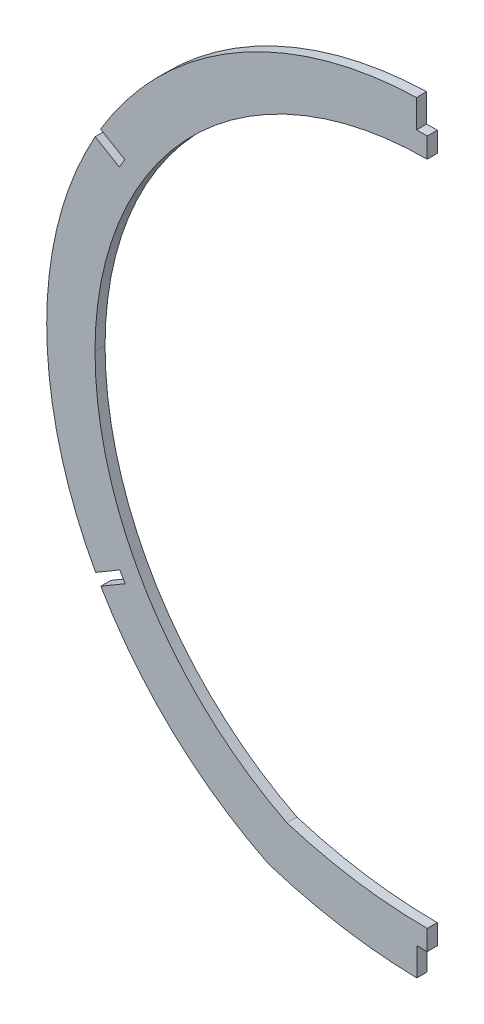
SolidWorks part; units mm, degrees
material "Balsa"
ref_plane "Front Plane" through (0, 0, 0) normal (0, 0, 1) x (1, 0, 0)
ref_plane "Top Plane" through (0, 0, 0) normal (0, 1, 0) x (1, 0, 0)
ref_plane "Right Plane" through (0, 0, 0) normal (1, 0, 0) x (0, 0, -1)
sketch "Sketch2" plane through (0, 0, 0) normal (0, 0, 1) x (1, 0, 0)
  line L0 (0, 0) -> (0.688, 245.4392) construction
  line L1 (-0.1309, -46.7153) -> (-0.2841, -101.3462) construction
  line L2 (0.0534, 19.05) -> (-169.3081, 19.05) construction
  line L3 (-72.7218, -93.726) -> (74.7111, -93.726) construction
  arc A1 (-120.0989, 19.05) -> (120.2036, 18.3433) centre (0.0534, 19.05) cw
  arc A2 (-120.0989, 19.05) -> (-50.0584, -93.726) centre (5.7147, 19.05) ccw
  arc A3 (-50.0584, -93.726) -> (50.1388, -93.726) centre (0.0402, 63.5) ccw
  arc A4 (120.2036, 18.3433) -> (50.1388, -93.726) centre (-5.6406, 19.0835) cw
  arc A5 (-104.8589, 19.05) -> (104.9639, 18.4329) centre (0.0534, 19.05) cw
  arc A6 (104.9639, 18.4329) -> (44.4049, -79.5534) centre (-5.6406, 19.0835) cw
  arc A7 (-44.324, -79.5535) -> (44.4049, -79.5534) centre (0.0402, 63.5) ccw
  arc A8 (-104.8589, 19.05) -> (-44.324, -79.5535) centre (5.7147, 19.05) ccw
  spline S0 degree 3 poles (-5521.0274, 5583.2546) (-1226.7801, 553.2855) (-196.9505, -260.8007) (69.4764, -82.4823) (75.8596, -77.7331) (81.7614, -72.3621) (85.2966, -68.8071) (85.996, -68.0862) (87.3792, -66.6243) (88.0639, -65.8824) (90.0847, -63.6371) (91.3894, -62.1126) (95.1787, -57.4581) (97.5389, -54.2471) (101.9343, -47.6137) (103.9694, -44.1914) (106.7765, -38.8981) (107.6712, -37.107) (109.3772, -33.4707) (110.1904, -31.6207) (112.481, -26.0415) (113.8153, -22.2742) (116.1105, -14.6467) (117.0712, -10.7866) (118.62, -2.9737) (119.208, 0.9791) (119.8028, 6.9796) (119.953, 8.9949) (120.1541, 13.0067) (120.2055, 15.0081) (120.2151, 20.9991) (119.8425, 28.9519) (118.7088, 36.835) (117.5685, 42.7208) (117.1399, 44.6783) (116.1841, 48.5842) (115.6559, 50.5346) (113.94, 56.3082) (112.6165, 60.0751) (109.6192, 67.4485) (107.9453, 71.055) (104.2453, 78.1066) (102.2192, 81.5518) (99.4588, 85.754) (98.8945, 86.5903) (97.7468, 88.2466) (97.1639, 89.0659) (95.3883, 91.4977) (94.1686, 93.0841) (90.4034, 97.7402) (87.752, 100.7072) (82.1689, 106.369) (79.2371, 109.0639) (74.6247, 112.8977) (73.0514, 114.1408) (70.6363, 115.9521) (69.821, 116.5478) (68.1799, 117.7153) (67.3537, 118.2875) (63.1947, 121.0918) (59.7778, 123.1535) (52.769, 126.9212) (49.1769, 128.6272) (41.816, 131.6806) (38.0473, 133.028) (33.2217, 134.4796) (32.2518, 134.758) (30.3116, 135.2882) (29.34, 135.5404) (26.4206, 136.2591) (24.4685, 136.6873) (18.5945, 137.8219) (14.6552, 138.3782) (6.7301, 139.0933) (2.7444, 139.252) (-2.2675, 139.1959) (-3.2714, 139.172) (-5.2821, 139.0983) (-6.2905, 139.0484) (-9.3072, 138.8606) (-11.3068, 138.6846) (-17.272, 138.0072) (-25.1357, 136.7069) (-32.823, 134.6274) (-38.5216, 132.7724) (-40.41, 132.1048) (-44.1641, 130.6694) (-46.0326, 129.9002) (-465.435, -55.3606) (264.7727, -2591.6725) (2155.1784, -7505.3224) knots -2.450405 -2.450405 -2.450405 -2.450405 0.03125 0.03125 0.0625 0.09375 0.09375 0.101563 0.101563 0.109375 0.109375 0.125 0.125 0.15625 0.15625 0.1875 0.1875 0.203125 0.203125 0.21875 0.21875 0.25 0.25 0.28125 0.28125 0.3125 0.3125 0.328125 0.328125 0.34375 0.34375 0.375 0.40625 0.40625 0.421875 0.421875 0.4375 0.4375 0.46875 0.46875 0.5 0.5 0.53125 0.53125 0.539063 0.539063 0.546875 0.546875 0.5625 0.5625 0.59375 0.59375 0.625 0.625 0.640625 0.640625 0.648438 0.648438 0.65625 0.65625 0.6875 0.6875 0.71875 0.71875 0.75 0.75 0.757813 0.757813 0.765625 0.765625 0.78125 0.78125 0.8125 0.8125 0.84375 0.84375 0.851563 0.851563 0.859375 0.859375 0.875 0.875 0.90625 0.9375 0.9375 0.953125 0.953125 0.96875 0.96875 4.508313 4.508313 4.508313 4.508313 only from (55.8537, -90.8749) to (-58.6671, 123.6507)
  spline S1 degree 3 poles (55.8537, -90.8749) (59.4151, -88.9779) (62.8499, -86.9173) (69.4764, -82.4823) (75.8596, -77.7331) (81.7614, -72.3621) (85.2966, -68.8071) (85.996, -68.0862) (87.3792, -66.6243) (88.0639, -65.8824) (90.0847, -63.6371) (91.3894, -62.1126) (95.1787, -57.4581) (97.5389, -54.2471) (101.9343, -47.6137) (103.9694, -44.1914) (106.7765, -38.8981) (107.6712, -37.107) (109.3772, -33.4707) (110.1904, -31.6207) (112.481, -26.0415) (113.8153, -22.2742) (116.1105, -14.6467) (117.0712, -10.7866) (118.62, -2.9737) (119.208, 0.9791) (119.8028, 6.9796) (119.953, 8.9949) (120.1541, 13.0067) (120.2055, 15.0081) (120.2151, 20.9991) (119.8425, 28.9519) (118.7088, 36.835) (117.5685, 42.7208) (117.1399, 44.6783) (116.1841, 48.5842) (115.6559, 50.5346) (113.94, 56.3082) (112.6165, 60.0751) (109.6192, 67.4485) (107.9453, 71.055) (104.2453, 78.1066) (102.2192, 81.5518) (99.4588, 85.754) (98.8945, 86.5903) (97.7468, 88.2466) (97.1639, 89.0659) (95.3883, 91.4977) (94.1686, 93.0841) (90.4034, 97.7402) (87.752, 100.7072) (82.1689, 106.369) (79.2371, 109.0639) (74.6247, 112.8977) (73.0514, 114.1408) (70.6363, 115.9521) (69.821, 116.5478) (68.1799, 117.7153) (67.3537, 118.2875) (63.1947, 121.0918) (59.7778, 123.1535) (52.769, 126.9212) (49.1769, 128.6272) (41.816, 131.6806) (38.0473, 133.028) (33.2217, 134.4796) (32.2518, 134.758) (30.3116, 135.2882) (29.34, 135.5404) (26.4206, 136.2591) (24.4685, 136.6873) (18.5945, 137.8219) (14.6552, 138.3782) (6.7301, 139.0933) (2.7444, 139.252) (-2.2675, 139.1959) (-3.2714, 139.172) (-5.2821, 139.0983) (-6.2905, 139.0484) (-9.3072, 138.8606) (-11.3068, 138.6846) (-17.272, 138.0072) (-25.1357, 136.7069) (-32.823, 134.6274) (-38.5216, 132.7724) (-40.41, 132.1048) (-44.1641, 130.6694) (-46.0326, 129.9002) (-51.5624, 127.4576) (-55.1595, 125.6458) (-58.6671, 123.6507) knots 0 0 0 0 0.03125 0.03125 0.0625 0.09375 0.09375 0.101563 0.101563 0.109375 0.109375 0.125 0.125 0.15625 0.15625 0.1875 0.1875 0.203125 0.203125 0.21875 0.21875 0.25 0.25 0.28125 0.28125 0.3125 0.3125 0.328125 0.328125 0.34375 0.34375 0.375 0.40625 0.40625 0.421875 0.421875 0.4375 0.4375 0.46875 0.46875 0.5 0.5 0.53125 0.53125 0.539063 0.539063 0.546875 0.546875 0.5625 0.5625 0.59375 0.59375 0.625 0.625 0.640625 0.640625 0.648438 0.648438 0.65625 0.65625 0.6875 0.6875 0.71875 0.71875 0.75 0.75 0.757813 0.757813 0.765625 0.765625 0.78125 0.78125 0.8125 0.8125 0.84375 0.84375 0.851563 0.851563 0.859375 0.859375 0.875 0.875 0.90625 0.9375 0.9375 0.953125 0.953125 0.96875 0.96875 1 1 1 1 construction
  spline S2 degree 3 poles (5694.5744, -5369.3669) (1292.3799, -516.6509) (187.1926, 314.492) (-76.9523, 111.0297) (-81.0984, 107.3558) (-85.9766, 102.3921) (-86.9369, 101.3807) (-88.8267, 99.3202) (-89.7577, 98.2691) (-92.4915, 95.0728) (-94.2304, 92.8907) (-99.2026, 86.1952) (-102.1931, 81.5333) (-106.1993, 74.2476) (-107.4545, 71.77) (-109.2154, 67.9791) (-109.782, 66.7031) (-110.874, 64.1258) (-111.4002, 62.8224) (-113.9097, 56.2871) (-115.5417, 50.9767) (-118.0823, 40.1978) (-118.9908, 34.7292) (-119.6657, 27.7928) (-119.7775, 26.4005) (-119.9543, 23.6055) (-120.0192, 22.2016) (-120.1418, 18.0057) (-120.1286, 15.2199) (-119.8102, 6.8959) (-119.2278, 1.3912) (-117.8014, -6.7994) (-117.2335, -9.5184) (-116.2404, -13.58) (-115.8858, -14.9311) (-115.1288, -17.6274) (-114.7258, -18.9739) (-112.6063, -25.6411) (-108.5276, -35.9696) (-103.1136, -45.6397) (-99.3011, -51.4722) (-98.5171, -52.628) (-96.9053, -54.9182) (-96.0765, -56.0537) (-93.5433, -59.4015) (-91.7865, -61.5635) (-86.3167, -67.8444) (-82.4051, -71.759) (-76.1398, -77.2217) (-73.9848, -78.9742) (-70.6503, -81.498) (-69.5218, -82.3217) (-67.2303, -83.9337) (-66.0665, -84.7222) (540.7318, -480.5341) (3882.3497, 5108.7967) (222.2795, -4616.5222) knots -3.63779 -3.63779 -3.63779 -3.63779 0.0625 0.0625 0.125 0.125 0.140625 0.140625 0.15625 0.15625 0.1875 0.1875 0.25 0.25 0.28125 0.28125 0.296875 0.296875 0.3125 0.3125 0.375 0.375 0.4375 0.4375 0.453125 0.453125 0.46875 0.46875 0.5 0.5 0.5625 0.5625 0.59375 0.59375 0.609375 0.609375 0.625 0.625 0.6875 0.75 0.75 0.765625 0.765625 0.78125 0.78125 0.8125 0.8125 0.875 0.875 0.90625 0.90625 0.921875 0.921875 0.9375 0.9375 9.012836 9.012836 9.012836 9.012836 only from (-58.6671, 123.6507) to (-50.3455, -93.5936)
  spline S3 degree 3 poles (-4578.1193, 6360.5009) (1102.8247, -3189.0685) (1357.3206, -1629.0846) (-2110.3169, 7551.2134) knots -196.711406 -196.711406 -196.711406 -196.711406 209.883914 209.883914 209.883914 209.883914 only from (49.819, -93.8744) to (55.8537, -90.8749)
  spline S4 degree 3 poles (49.819, -93.8744) (51.8584, -92.9316) (53.87, -91.9317) (55.8537, -90.8749) knots 0 0 0 0 1 1 1 1 construction
  spline S5 degree 3 poles (-58.6671, 123.6507) (-63.5487, 120.874) (-68.1774, 117.7887) (-76.9523, 111.0297) (-81.0984, 107.3558) (-85.9766, 102.3921) (-86.9369, 101.3807) (-88.8267, 99.3202) (-89.7577, 98.2691) (-92.4915, 95.0728) (-94.2304, 92.8907) (-99.2026, 86.1952) (-102.1931, 81.5333) (-106.1993, 74.2476) (-107.4545, 71.77) (-109.2154, 67.9791) (-109.782, 66.7031) (-110.874, 64.1258) (-111.4002, 62.8224) (-113.9097, 56.2871) (-115.5417, 50.9767) (-118.0823, 40.1978) (-118.9908, 34.7292) (-119.6657, 27.7928) (-119.7775, 26.4005) (-119.9543, 23.6055) (-120.0192, 22.2016) (-120.1418, 18.0057) (-120.1286, 15.2199) (-119.8102, 6.8959) (-119.2278, 1.3912) (-117.8014, -6.7994) (-117.2335, -9.5184) (-116.2404, -13.58) (-115.8858, -14.9311) (-115.1288, -17.6274) (-114.7258, -18.9739) (-112.6063, -25.6411) (-108.5276, -35.9696) (-103.1136, -45.6397) (-99.3011, -51.4722) (-98.5171, -52.628) (-96.9053, -54.9182) (-96.0765, -56.0537) (-93.5433, -59.4015) (-91.7865, -61.5635) (-86.3167, -67.8444) (-82.4051, -71.759) (-76.1398, -77.2217) (-73.9848, -78.9742) (-70.6503, -81.498) (-69.5218, -82.3217) (-67.2303, -83.9337) (-66.0665, -84.7222) (-60.2073, -88.5441) (-55.3561, -91.2432) (-50.3455, -93.5936) knots 0 0 0 0 0.0625 0.0625 0.125 0.125 0.140625 0.140625 0.15625 0.15625 0.1875 0.1875 0.25 0.25 0.28125 0.28125 0.296875 0.296875 0.3125 0.3125 0.375 0.375 0.4375 0.4375 0.453125 0.453125 0.46875 0.46875 0.5 0.5 0.5625 0.5625 0.59375 0.59375 0.609375 0.609375 0.625 0.625 0.6875 0.75 0.75 0.765625 0.765625 0.78125 0.78125 0.8125 0.8125 0.875 0.875 0.90625 0.90625 0.921875 0.921875 0.9375 0.9375 1 1 1 1 construction
  spline S6 degree 3 poles (-1759.0643, 7695.5768) (129.301, 75.0658) (104.9025, -75.6984) (45.8458, -95.3665) (44.8322, -95.6594) (41.7708, -96.4587) (39.7032, -96.8873) (35.5384, -97.6293) (33.4392, -97.9405) (29.2422, -98.4783) (27.1412, -98.7049) (20.8322, -99.2882) (16.6185, -99.55) (8.1799, -99.8877) (3.9548, -99.9623) (-4.5058, -99.9387) (-8.734, -99.8405) (-17.1695, -99.4557) (-21.3793, -99.1705) (-27.6778, -98.553) (-29.7745, -98.3152) (-33.9608, -97.7556) (-36.0504, -97.4344) (-39.177, -96.8603) (-40.2191, -96.653) (-42.292, -96.1992) (-43.3225, -95.953) (-45.3676, -95.407) (-46.3821, -95.1076) (-105.8729, -74.9194) (-124.4058, 77.5041) (2082.3243, 7613.4914) knots -1.777254 -1.777254 -1.777254 -1.777254 0.03125 0.03125 0.0625 0.0625 0.125 0.125 0.1875 0.1875 0.25 0.25 0.375 0.375 0.5 0.5 0.625 0.625 0.75 0.75 0.8125 0.8125 0.875 0.875 0.90625 0.90625 0.9375 0.9375 0.96875 0.96875 2.792352 2.792352 2.792352 2.792352 only from (49.8185, -93.8746) to (-50.3451, -93.5938)
  spline S7 degree 3 poles (49.8185, -93.8746) (48.8452, -94.325) (47.8521, -94.6984) (45.8458, -95.3665) (44.8322, -95.6594) (41.7708, -96.4587) (39.7032, -96.8873) (35.5384, -97.6293) (33.4392, -97.9405) (29.2422, -98.4783) (27.1412, -98.7049) (20.8322, -99.2882) (16.6185, -99.55) (8.1799, -99.8877) (3.9548, -99.9623) (-4.5058, -99.9387) (-8.734, -99.8405) (-17.1695, -99.4557) (-21.3793, -99.1705) (-27.6778, -98.553) (-29.7745, -98.3152) (-33.9608, -97.7556) (-36.0504, -97.4344) (-39.177, -96.8603) (-40.2191, -96.653) (-42.292, -96.1992) (-43.3225, -95.953) (-45.3676, -95.407) (-46.3821, -95.1076) (-48.3867, -94.4274) (-49.3773, -94.0483) (-50.3451, -93.5938) knots 0 0 0 0 0.03125 0.03125 0.0625 0.0625 0.125 0.125 0.1875 0.1875 0.25 0.25 0.375 0.375 0.5 0.5 0.625 0.625 0.75 0.75 0.8125 0.8125 0.875 0.875 0.90625 0.90625 0.9375 0.9375 0.96875 0.96875 1 1 1 1 construction
  spline S8 degree 1 poles (44.4895, -82.3468) (49.8828, -79.6661) knots 0 0 1 1 construction
  spline S9 degree 1 poles (49.8828, -79.6661) (-52.388, 112.6115) knots 0 0 1 1 construction
  spline S10 degree 1 poles (-52.388, 112.6115) (-44.952, -82.0958) knots 0 0 1 1 construction
  spline S11 degree 3 poles (44.4895, -82.3468) (44.9451, -82.1361) (45.8533, -81.7084) (47.2062, -81.0479) (48.5497, -80.3682) (49.4396, -79.9022) (49.8828, -79.6661) knots 0 0 0 0 0.250007 0.500014 0.750021 1.000028 1.000028 1.000028 1.000028 construction
  spline S12 degree 3 poles (49.8828, -79.6661) (51.4682, -78.8216) (54.6039, -77.0481) (60.6329, -73.2256) (67.7713, -67.9145) (75.6946, -60.7068) (85.376, -49.946) (92.2499, -39.5527) (97.0635, -29.9209) (99.9774, -23.2906) (102.9687, -14.8438) (105.5551, -4.452) (106.8747, 4.4138) (107.4138, 11.642) (107.598, 18.8242) (107.1791, 27.7507) (105.6575, 38.3493) (103.0737, 48.9109) (99.5091, 59.0529) (95.0071, 68.7524) (90.4672, 76.4728) (86.3465, 82.4205) (79.7918, 90.9419) (71.0678, 99.805) (59.5047, 108.4813) (50.3361, 114.0108) (40.7123, 118.5824) (32.2831, 121.5955) (25.3334, 123.4944) (18.366, 125.0225) (9.571, 126.2643) (-1.0997, 126.6912) (-11.9104, 126.0185) (-22.4327, 124.2743) (-36.1547, 120.5693) (-46.1487, 116.1604) (-52.388, 112.6115) knots 0 0 0 0 0.015625 0.03125 0.0625 0.09375 0.125 0.1875 0.203125 0.21875 0.25 0.28125 0.3125 0.328125 0.34375 0.375 0.40625 0.4375 0.46875 0.5 0.53125 0.546875 0.5625 0.625 0.65625 0.6875 0.71875 0.75 0.765625 0.78125 0.8125 0.84375 0.875 0.90625 0.9375 1 1 1 1 construction
  spline S13 degree 3 poles (-52.388, 112.6115) (-54.5585, 111.3769) (-58.8261, 108.7475) (-66.8816, 102.9693) (-76.1597, 94.757) (-85.9932, 83.258) (-92.681, 72.8203) (-97.1816, 63.9424) (-101.112, 54.6656) (-104.776, 42.7383) (-106.8137, 30.488) (-107.4512, 20.4245) (-107.4028, 10.4189) (-106.3564, 0.5368) (-104.3212, -9.2152) (-101.5955, -18.9231) (-97.0158, -30.5128) (-90.9605, -41.334) (-85.1677, -49.567) (-78.8706, -57.3154) (-71.8665, -64.3232) (-64.1621, -70.5906) (-57.9948, -74.9291) (-51.5954, -78.7902) (-47.193, -81.0446) (-44.952, -82.0958) knots 0 0 0 0 0.03125 0.0625 0.125 0.1875 0.25 0.28125 0.3125 0.375 0.4375 0.46875 0.5 0.5625 0.59375 0.625 0.6875 0.75 0.78125 0.8125 0.875 0.90625 0.9375 0.96875 1 1 1 1 construction
  spline S14 degree 1 poles (44.4849, -82.3489) (-44.9469, -82.0982) knots 0 0 1 1 construction
  spline S15 degree 3 poles (44.4849, -82.3489) (44.3746, -82.3999) (44.1627, -82.4934) (43.6492, -82.7012) (42.8561, -82.9839) (41.7841, -83.3184) (40.2245, -83.7477) (38.1103, -84.2445) (35.4106, -84.7656) (32.6063, -85.224) (28.7759, -85.7537) (23.885, -86.2821) (17.9201, -86.7432) (11.8971, -87.0512) (5.8396, -87.2261) (-2.2666, -87.2864) (-10.3738, -87.0974) (-18.3985, -86.6419) (-24.3556, -86.1481) (-29.2377, -85.5934) (-33.056, -85.0443) (-35.8555, -84.5718) (-38.5671, -84.0318) (-40.6899, -83.5223) (-42.2517, -83.0828) (-43.3238, -82.7417) (-44.1147, -82.4546) (-44.6269, -82.2439) (-44.8373, -82.1497) (-44.9469, -82.0982) knots 0 0 0 0 0.007812 0.015625 0.03125 0.046875 0.0625 0.09375 0.125 0.15625 0.1875 0.25 0.3125 0.375 0.4375 0.5 0.625 0.6875 0.75 0.8125 0.84375 0.875 0.90625 0.9375 0.953125 0.96875 0.984375 0.992188 1 1 1 1 construction
  point P12 (-0.2802, -99.9505)
  dimension "D3" = 19.05
  dimension "D4" = 93.726
  dimension "D5" = 63.5
  dimension "D6" = 15.24
  dimension "D1" = 12.7
  dimension "D2" = 12.7
extrude "Boss-Extrude1" add sketch "Sketch2" along normal mid plane 3.175
sketch "Sketch3" plane through (0, 0, 0) normal (1, 0, 0) x (0, 0, -1)
  line L1 (-100.0568, 212.3798) -> (108.5889, 212.3798)
  line L2 (-100.0568, 212.3798) -> (-100.0568, -170.6472)
  line L3 (-100.0568, -170.6472) -> (108.5889, -170.6472)
  line L4 (108.5889, 212.3798) -> (108.5889, -170.6472)
extrude "Cut-Extrude1" cut sketch "Sketch3" along normal through all
sketch "Sketch4" plane through (0, 0, 1.5875) normal (0, 0, 1) x (1, 0, 0)
  line L0 (0, 0) -> (0, 123.9623) construction
  line L1 (0, 123.9623) -> (0, 130.3123) construction
  line L2 (-3.3782, 130.3123) -> (3.3782, 130.3123)
  line L3 (0, 130.3123) -> (0, 143.0123)
  line L4 (3.3782, 130.3123) -> (3.3782, 143.0123)
  line L5 (-3.3782, 143.0123) -> (3.3782, 143.0123)
  line L6 (90.8212, 71.4752) -> (96.2977, 74.6892) construction
  line L7 (95.4428, 76.146) -> (97.1526, 73.2325)
  line L8 (90.8212, 71.4752) -> (0, 18.1749) construction
  line L9 (95.4428, 76.146) -> (106.3959, 82.5741)
  line L10 (97.1526, 73.2325) -> (108.1057, 79.6605)
  line L11 (106.3959, 82.5741) -> (108.1057, 79.6605)
  line L12 (90.7135, -35.0622) -> (96.19, -38.2762) construction
  line L13 (90.7135, -35.0622) -> (0, 18.1749) construction
  line L14 (95.3351, -39.733) -> (97.045, -36.8194)
  line L15 (95.3351, -39.733) -> (106.2882, -46.161)
  line L16 (97.045, -36.8194) -> (107.998, -43.2475)
  line L17 (106.2882, -46.161) -> (107.998, -43.2475)
  line L18 (0, 0) -> (0, -86.2748) construction
  line L19 (0, -86.2748) -> (0, -92.6248) construction
  line L20 (-3.302, -92.6248) -> (3.302, -92.6248)
  line L21 (0, -92.6248) -> (0, -105.3248)
  line L22 (3.302, -92.6248) -> (3.302, -105.3248)
  line L23 (-3.302, -105.3248) -> (3.302, -105.3248)
  line L24 (-90.7135, -35.0622) -> (0, 18.1749) construction
  line L25 (-90.7135, -35.0622) -> (-96.19, -38.2762) construction
  line L26 (-90.8212, 71.4752) -> (0, 18.1749) construction
  line L27 (-90.8212, 71.4752) -> (-96.2977, 74.6892) construction
  line L28 (-3.302, -92.6248) -> (-3.302, -105.3248)
  line L29 (-106.2882, -46.161) -> (-107.998, -43.2475)
  line L30 (-97.045, -36.8194) -> (-107.998, -43.2475)
  line L31 (-95.3351, -39.733) -> (-106.2882, -46.161)
  line L32 (-95.3351, -39.733) -> (-97.045, -36.8194)
  line L33 (-106.3959, 82.5741) -> (-108.1057, 79.6605)
  line L34 (-97.1526, 73.2325) -> (-108.1057, 79.6605)
  line L35 (-95.4428, 76.146) -> (-106.3959, 82.5741)
  line L36 (-95.4428, 76.146) -> (-97.1526, 73.2325)
  line L37 (-3.3782, 130.3123) -> (-3.3782, 143.0123)
  point P2 (96.2977, 74.6892)
  point P10 (96.19, -38.2762)
  point P26 (0, 0)
  point P44 (0, 0)
  point P45 (-90.713, -35.063)
  point P46 (-90.7135, 71.6614)
  arc M24 (-50.0584, -93.726) -> (0, -101.5148) centre (0.0402, 63.5) ccw
  line M25 (0, -101.5148) -> (0, -86.2748)
  line M29 (0, 123.9623) -> (0, 139.2023)
  arc M30 (0, 139.2023) -> (-120.0989, 19.05) centre (0.0534, 19.05) ccw
  arc M31 (-120.0989, 19.05) -> (-50.0584, -93.726) centre (5.7147, 19.05) ccw
  dimension "D1" = 123.9623
  dimension "D2" = 6.35
  dimension "D3" = 3.3782
  dimension "D4" = 12.7
  dimension "D5" = 59.593
  dimension "D6" = 18.1749
  dimension "D7" = 105.3062
  dimension "D8" = 6.35
  dimension "D9" = 3.3782
  dimension "D10" = 12.7
  dimension "D11" = 59.593
  dimension "D12" = 105.1814
  dimension "D13" = 6.35
  dimension "D14" = 12.7
  dimension "D15" = 3.3782
  dimension "D16" = 6.35
  dimension "D17" = 86.2748
  dimension "D18" = 3.302
  dimension "D19" = 12.7
extrude "Cut-Extrude2" cut sketch "Sketch4" against normal through all contours L36 L35 L34 M30 | L37 L2 M29 M30 | L31 L32 L30 M31 | L20 L28 M24 M25 region at (-1.6875, 134.749, 1.5875) region at (-1.65, -97.0641, 1.5875) region at (-100.0221, -40.5273, 1.5875) region at (-100.1294, 76.9388, 1.5875)
